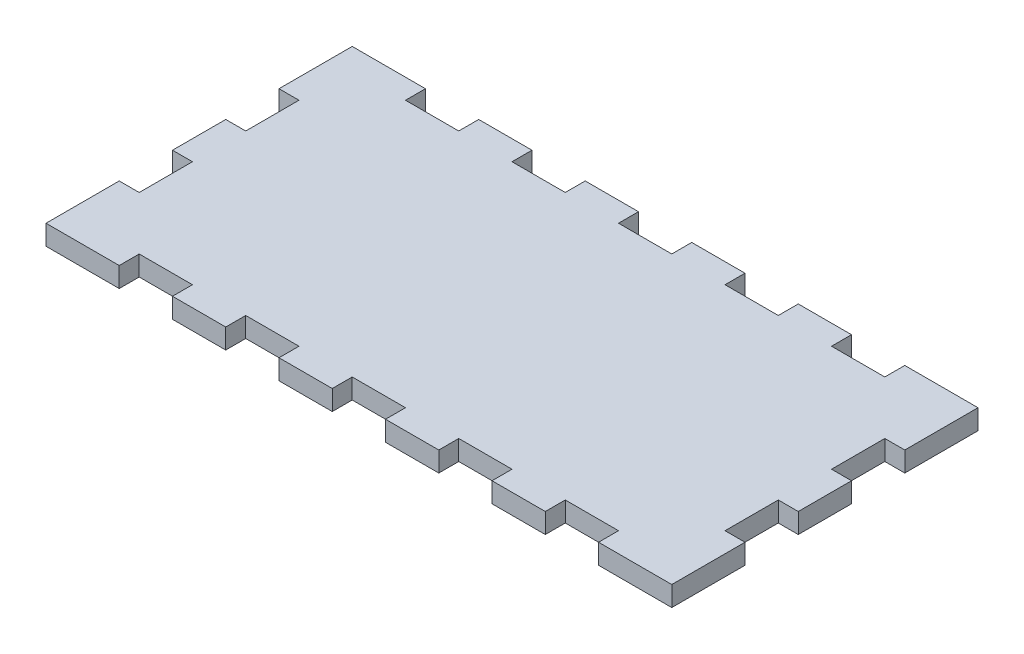
SolidWorks part; units mm, degrees
ref_plane "Front Plane" through (0, 0, 0) normal (0, 0, 1) x (1, 0, 0)
ref_plane "Top Plane" through (0, 0, 0) normal (0, 1, 0) x (1, 0, 0)
ref_plane "Right Plane" through (0, 0, 0) normal (1, 0, 0) x (0, 0, -1)
sketch "Sketch2" plane through (0, 0, 0) normal (0, 1, 0) x (1, 0, 0)
  line L1 (139.7, -63.5) -> (-139.7, -63.5)
  line L2 (139.7, -63.5) -> (139.7, 63.5)
  line L3 (139.7, 63.5) -> (-139.7, 63.5)
  line L4 (-139.7, -63.5) -> (-139.7, 63.5)
  line L5 (139.7, -63.5) -> (-139.7, 63.5) construction
  line L6 (139.7, 63.5) -> (-139.7, -63.5) construction
  point P0 (0, 0)
  dimension "D1" = 279.4
  dimension "D2" = 127
extrude "Boss-Extrude1" add sketch "Sketch2" along normal blind 9.525
sketch "Sketch3" plane through (0, 0, 63.5) normal (0, 0, 1) x (1, 0, 0)
  line L0 (-139.7, 9.525) -> (139.7, 9.525) construction
  line L1 (-139.7, 0) -> (-114.3, 0)
  line L2 (-139.7, 0) -> (-139.7, 9.525)
  line L3 (-139.7, 9.525) -> (-114.3, 9.525)
  line L4 (-114.3, 0) -> (-114.3, 9.525)
  dimension "D1" = 25.4
extrude "Boss-Extrude2" add sketch "Sketch3" along normal blind 9.525
pattern_linear "LPattern1" count 6 spacing 50.8 along (1, 0, 0) of "Boss-Extrude2"
mirror "Mirror1" about plane through (0, 0, 0) normal (0, 0, 1) of "LPattern1"
sketch "Sketch4" plane through (139.7, 0, 0) normal (1, 0, 0) x (0, 0, -1)
  line L0 (-73.025, 0) -> (73.025, 0) construction
  line L1 (-63.5, 0) -> (-38.1, 0)
  line L2 (-63.5, 0) -> (-63.5, 9.525)
  line L3 (-63.5, 9.525) -> (-38.1, 9.525)
  line L4 (-38.1, 0) -> (-38.1, 9.525)
  line L5 (-73.025, 9.525) -> (73.025, 9.525) construction
  line L6 (-73.025, 0) -> (-73.025, 9.525) construction
  dimension "D1" = 9.525
  dimension "D2" = 25.4
extrude "Boss-Extrude3" add sketch "Sketch4" along normal blind 9.525
pattern_linear "LPattern2" count 3 spacing 50.8 along (0, 0, -1) of "Boss-Extrude3"
mirror "Mirror2" about plane through (0, 0, 0) normal (1, 0, 0) of "LPattern2"
sketch "Sketch6" plane through (0, 0, 63.5) normal (0, 0, 1) x (1, 0, 0)
  line L1 (149.225, 9.525) -> (139.7, 9.525)
  line L2 (149.225, 9.525) -> (149.225, 0)
  line L3 (149.225, 0) -> (139.7, 0)
  line L4 (139.7, 9.525) -> (139.7, 0)
extrude "Boss-Extrude4" add sketch "Sketch6" along normal blind 9.525
mirror "Mirror3" about plane through (0, 0, 0) normal (1, 0, 0) of "Boss-Extrude4"
mirror "Mirror4" about plane through (0, 0, 0) normal (0, 0, 1) of "Mirror3"
sketch "Sketch7" plane through (0, 9.525, 0) normal (0, 1, 0) x (1, 0, 0)
  circle A0 centre (-29.2864, 23.8119) radius 0.032
  circle A1 centre (-23.072, 14.7922) radius 0.1056
  circle A2 centre (27.5, 22.9863) radius 2
  circle A3 centre (22.5, 12.9863) radius 2
extrude "Cut-Extrude1" [suppressed] cut sketch "Sketch7" against normal through all
sketch "Sketch8" plane through (0, 9.525, 0) normal (0, 1, 0) x (1, 0, 0)
  circle A0 centre (-25.974, 23.4033) radius 0.0509
  circle A1 centre (-24.0521, 14.3728) radius 0.0812
  circle A2 centre (-27.5, -15.3245) radius 2
  circle A3 centre (-22.5, -25.3245) radius 2
extrude "Cut-Extrude3" [suppressed] cut sketch "Sketch8" against normal through all contours A2 A0 | A3
sketch "Sketch9" [suppressed] plane through (0, 0, 0) normal (0, -1, 0) x (1, 0, 0)
  circle A0 centre (-22.5, -12.9863) radius 3.81
  circle A1 centre (-27.5, -22.9863) radius 3.81
  circle A2 centre (22.5, -12.9863) radius 3.81
  circle A3 centre (27.5, -22.9863) radius 3.81
  dimension "D1" = 7.62
  dimension "D2" = 7.62
  dimension "D3" = 7.62
  dimension "D4" = 7.62
extrude "Cut-Extrude4" [suppressed] cut sketch "Sketch9" against normal blind 4.7625
